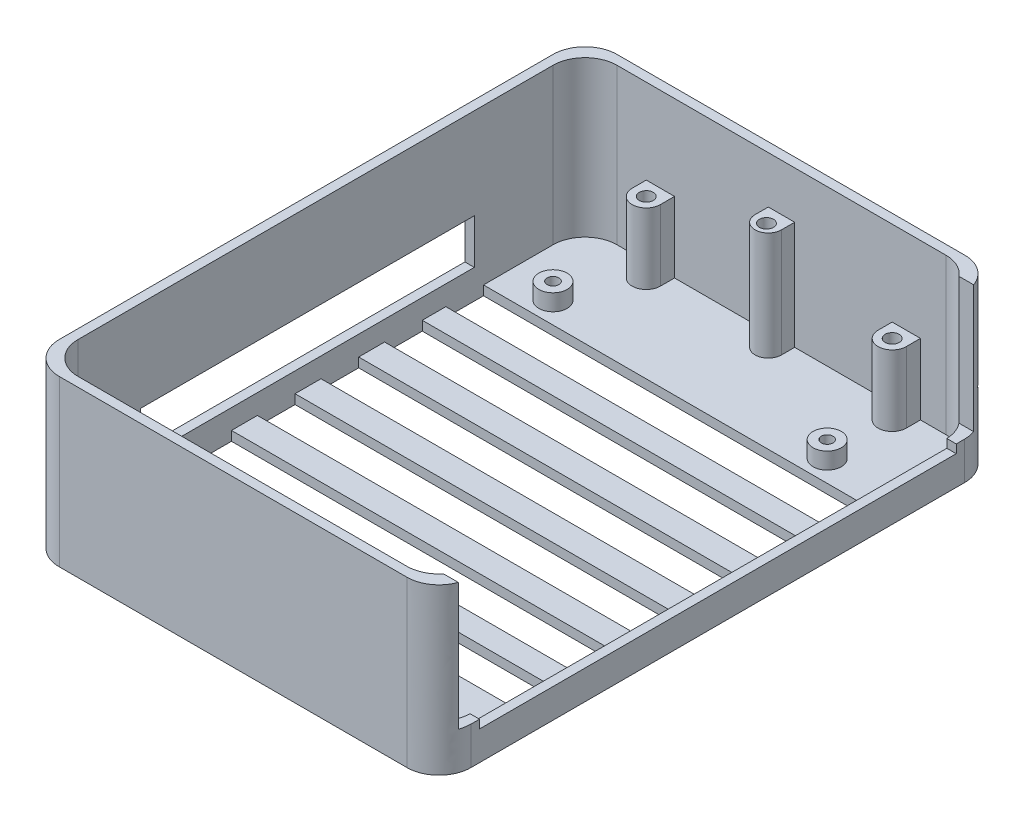
SolidWorks part; units mm, degrees
ref_plane "Front Plane" through (0, 0, 0) normal (0, 0, 1) x (1, 0, 0)
ref_plane "Top Plane" through (0, 0, 0) normal (0, 1, 0) x (1, 0, 0)
ref_plane "Right Plane" through (0, 0, 0) normal (1, 0, 0) x (0, 0, -1)
sketch "Sketch1" plane through (0, 0, 0) normal (0, 1, 0) x (1, 0, 0)
  line L1 (43.7, -59.2) -> (-43.7, -59.2)
  line L2 (43.7, -59.2) -> (43.7, 59.2)
  line L3 (43.7, 59.2) -> (-43.7, 59.2)
  line L4 (-43.7, -59.2) -> (-43.7, 59.2)
  line L5 (43.7, -59.2) -> (-43.7, 59.2) construction
  line L6 (43.7, 59.2) -> (-43.7, -59.2) construction
  point P0 (0, 0)
  dimension "D1" = 118.4
  dimension "D2" = 87.4
extrude "Boss-Extrude1" add sketch "Sketch1" along normal blind 35
sketch "Sketch2" plane through (0, 35, 0) normal (0, 1, 0) x (1, 0, 0)
  line L0 (-43.7, 59.2) -> (-43.7, -59.2) construction
  line L2 (43.7, -59.2) -> (43.7, 59.2) construction
  line L3 (-43.7, -59.2) -> (43.7, -59.2) construction
  line L4 (43.7, 59.2) -> (-43.7, 59.2) construction
  line L5 (-43.7, 59.2) -> (-43.7, -59.2) construction
  line L6 (43.7, -59.2) -> (43.7, 59.2) construction
  line L7 (-43.7, -59.2) -> (43.7, -59.2) construction
  line L8 (43.7, 59.2) -> (-43.7, 59.2) construction
  line L10 (41.7, -57.2) -> (-41.7, -57.2)
  line L11 (41.7, -57.2) -> (41.7, 57.2)
  line L12 (41.7, 57.2) -> (-41.7, 57.2)
  line L13 (-41.7, -57.2) -> (-41.7, 57.2)
  line L14 (41.7, -57.2) -> (-41.7, 57.2) construction
  line L15 (41.7, 57.2) -> (-41.7, -57.2) construction
  point P5 (0, 0)
  dimension "D1" = 2
  dimension "D2" = 2
extrude "Cut-Extrude1" cut sketch "Sketch2" against normal blind 33
sketch "Sketch3" plane through (43.7, 0, 0) normal (1, 0, 0) x (0, 0, -1)
  line L0 (54.7, 35) -> (54.7, 8)
  line L1 (-59.2, 35) -> (59.2, 35) construction
  line L3 (54.7, 8) -> (50.6, 8)
  line L4 (50.6, 8) -> (50.6, 6.2)
  line L5 (50.6, 6.2) -> (-50.6, 6.2)
  line L6 (0, -0.5379) -> (0, 35) construction
  line L7 (-54.7, 35) -> (-54.7, 8)
  line L8 (-54.7, 8) -> (-50.6, 8)
  line L9 (-50.6, 8) -> (-50.6, 6.2)
  line L10 (-59.2, 0) -> (59.2, 0) construction
  point P16 (0, 6.2)
  dimension "D1" = 4.5
  dimension "D2" = 27
  dimension "D3" = 4.1
  dimension "D4" = 1.8
extrude "Cut-Extrude2" cut sketch "Sketch3" against normal blind 33 and the other way through all
fillet "Fillet1" radius 6.8 8 edges at (41.7, 18.5, 57.2) (-41.7, 18.5, -57.2) (-41.7, 18.5, 57.2) (41.7, 18.5, -57.2) (-43.7, 17.5, -59.2) (43.7, 17.5, -59.2) (43.7, 17.5, 59.2) (-43.7, 17.5, 59.2) first distance on face at (0, 18.5, 57.2) first distance on face at (0, 18.5, -57.2) first distance on face at (-41.7, 18.5, 0) first distance on face at (41.7, 15.7, 0) first distance on face at (-43.7, 17.5, 0) first distance on face at (43.7, 15.3667, 0)
sketch "Sketch4" plane through (0, 2, 0) normal (0, 1, 0) x (1, 0, 0)
  line L0 (41.7, 40.2) -> (26.7, 40.2) construction
  line L1 (41.7, 50.4) -> (41.7, -50.4) construction
  line L2 (36.9, 59.2) -> (-36.9, 59.2) construction
  line L3 (26.7, 40.2) -> (-31.5, 40.2) construction
  line L5 (-31.5, 40.2) -> (-31.5, -45.9) construction
  line L6 (26.7, 40.2) -> (26.7, -45.9) construction
  circle A0 centre (-31.5, 40.2) radius 1.25
  circle A1 centre (26.7, 40.2) radius 1.25
  circle A2 centre (-31.5, -45.9) radius 1.25
  circle A3 centre (26.7, -45.9) radius 1.25
  circle A4 centre (-31.5, -45.9) radius 3
  circle A5 centre (26.7, -45.9) radius 3
  circle A6 centre (26.7, 40.2) radius 3
  circle A7 centre (-31.5, 40.2) radius 3
  dimension "D4" = 2.5
  dimension "D5" = 2.5
  dimension "D7" = 2.5
  dimension "D8" = 2.5
  dimension "D9" = 6
  dimension "D10" = 6
  dimension "D11" = 6
  dimension "D12" = 6
  dimension "D1" = 15
  dimension "D2" = 19
  dimension "D3" = 58.2
  dimension "D6" = 86.1
  dimension "D13" = 86.1
extrude "Boss-Extrude2" add sketch "Sketch4" along normal blind 3.5
sketch "Sketch5" plane through (0, 2, 0) normal (0, 1, 0) x (1, 0, 0)
  line L0 (-25.7, -59) -> (-25.7, -54) construction
  line L2 (-25.7, -54) -> (-43.7, -54) construction
  line L3 (-43.7, 52.4) -> (-43.7, -52.4) construction
  line L4 (-25.7, -54) -> (26.3, -54) construction
  line L5 (-25.7, 59.2) -> (-25.7, 54.2) construction
  line L6 (36.9, 59.2) -> (-36.9, 59.2) construction
  line L7 (-25.7, 54.2) -> (26.5, 54.2) construction
  line L9 (-28.7, 54.2) -> (-28.7, 57.2)
  line L10 (-34.9, -57.2) -> (34.9, -57.2) construction
  line L11 (34.9, 57.2) -> (-34.9, 57.2) construction
  line L12 (-22.7, 54.2) -> (-22.7, 57.2)
  line L13 (34.9, 57.2) -> (-34.9, 57.2) construction
  line L14 (23.5, 54.2) -> (23.5, 57.2)
  line L15 (29.5, 54.2) -> (29.5, 57.2)
  line L16 (-28.7, -54) -> (-28.7, -57.2)
  line L17 (-34.9, -57.2) -> (34.9, -57.2) construction
  line L18 (-22.7, -54) -> (-22.7, -57.2)
  line L19 (23.3, -54) -> (23.3, -57.2)
  line L20 (29.3, -54) -> (29.3, -57.2)
  line L21 (-28.7, -57.2) -> (-22.7, -57.2)
  line L22 (23.3, -57.2) -> (29.3, -57.2)
  line L23 (23.5, 57.2) -> (29.5, 57.2)
  line L24 (-28.7, 57.2) -> (-22.7, 57.2)
  circle A0 centre (-25.7, -54) radius 1.5
  circle A1 centre (26.3, -54) radius 1.5
  arc A2 (-22.7, -54) -> (-28.7, -54) centre (-25.7, -54) ccw
  arc A3 (29.3, -54) -> (23.3, -54) centre (26.3, -54) ccw
  circle A5 centre (26.5, 54.2) radius 1.5
  arc A6 (23.5, 54.2) -> (29.5, 54.2) centre (26.5, 54.2) ccw
  circle A7 centre (-25.7, 54.2) radius 1.5
  arc A8 (-28.7, 54.2) -> (-22.7, 54.2) centre (-25.7, 54.2) ccw
  dimension "D4" = 3
  dimension "D5" = 3
  dimension "D6" = 6
  dimension "D7" = 6
  dimension "D9" = 3
  dimension "D10" = 6
  dimension "D11" = 3
  dimension "D12" = 6
  dimension "D1" = 18
  dimension "D2" = 5
  dimension "D3" = 52
  dimension "D8" = 5
extrude "Boss-Extrude4" add sketch "Sketch5" along normal blind 15
sketch "Sketch7" plane through (0, 2, 0) normal (0, 1, 0) x (1, 0, 0)
  circle A0 centre (-25.7, 54.2) radius 1.5 construction
  circle A1 centre (-25.7, 54.2) radius 1.5
  circle A2 centre (26.5, 54.2) radius 1.5 construction
  circle A3 centre (26.5, 54.2) radius 1.5
  circle A4 centre (-25.7, -54) radius 1.5 construction
  circle A5 centre (-25.7, -54) radius 1.5
  circle A6 centre (26.3, -54) radius 1.5 construction
  circle A7 centre (26.3, -54) radius 1.5
extrude "Cut-Extrude3" cut sketch "Sketch7" against normal blind 20
sketch "Sketch9" plane through (0, 2, 0) normal (0, 1, 0) x (1, 0, 0)
  line L0 (0, 57.2) -> (0, -59.2) construction
  line L2 (-36.9, -59.2) -> (36.9, -59.2) construction
  line L3 (0, 57.2) -> (-2.8, 57.2)
  line L5 (34.9, 57.2) -> (-34.9, 57.2) construction
  line L6 (0, 57.2) -> (2.8, 57.2)
  line L7 (-2.8, 57.2) -> (-2.8, 54.4)
  line L8 (2.8, 57.2) -> (2.8, 54.4)
  line L10 (-3, -57.2) -> (-3, -54.4)
  line L12 (2.6, -57.2) -> (2.6, -54.4)
  line L13 (-34.9, -57.2) -> (34.9, -57.2) construction
  line L14 (-3, -57.2) -> (2.6, -57.2)
  line L15 (-2.8, 54.4) -> (2.8, 54.4)
  line L16 (-3, -54.4) -> (2.6, -54.4)
  dimension "D5" = 2.8
  dimension "D1" = 2.8
  dimension "D2" = 2.8
  dimension "D3" = 2.8
  dimension "D4" = 2.8
  dimension "D6" = 5.6
extrude "Boss-Extrude5" add sketch "Sketch9" along normal blind 23
sketch "Sketch10" plane through (0, 2, 0) normal (0, 1, 0) x (1, 0, 0)
  line L3 (2.6, -54.4) -> (-3, -54.4) construction
  line L8 (-3, -54.4) -> (2.6, -54.4)
  line L9 (-2.8, 54.4) -> (2.8, 54.4) construction
  line L12 (-2.8, 54.4) -> (2.8, 54.4)
  arc A3 (2.6, -54.4) -> (-3, -54.4) centre (-0.2, -54.4) ccw
  arc A4 (-2.8, 54.4) -> (2.8, 54.4) centre (0, 54.4) ccw
  dimension "D1" = 5.6
extrude "Boss-Extrude6" add sketch "Sketch10" along normal blind 23
sketch "Sketch11" plane through (0, 25, 0) normal (0, 1, 0) x (1, 0, 0)
  line L0 (0, 57.2) -> (0, 54.0044) construction
  line L1 (2.8, 57.2) -> (-2.8, 57.2) construction
  line L2 (0, -57.2) -> (0, -54.2) construction
  line L3 (-34.9, -57.2) -> (34.9, -57.2) construction
  circle A0 centre (0, 54.0044) radius 1.5
  circle A1 centre (0, -54.2) radius 1.5
  dimension "D1" = 3
  dimension "D3" = 3
  dimension "D2" = 3
extrude "Cut-Extrude4" cut sketch "Sketch11" against normal blind 17
sketch "Sketch12" plane through (0, 2, 0) normal (0, 1, 0) x (1, 0, 0)
  line L0 (-41.7, 50.4) -> (-41.7, -50.4) construction
  line L1 (-41.7, -38.8457) -> (41.7, -38.8457)
  line L2 (-41.7, -38.8457) -> (-41.7, -30.8457)
  line L3 (-41.7, -30.8457) -> (41.7, -30.8457)
  line L4 (41.7, -38.8457) -> (41.7, -30.8457)
  line L5 (41.7, 50.4) -> (41.7, -50.4) construction
  line L6 (41.7, -50.4) -> (41.7, 50.4) construction
  line L7 (-41.7, -25.8457) -> (41.7, -25.8457)
  line L8 (-41.7, -25.8457) -> (-41.7, -17.8457)
  line L9 (-41.7, -17.8457) -> (41.7, -17.8457)
  line L10 (41.7, -25.8457) -> (41.7, -17.8457)
  line L11 (-41.7, -12.3457) -> (41.7, -12.3457)
  line L12 (-41.7, -12.3457) -> (-41.7, -4.3457)
  line L13 (-41.7, -4.3457) -> (41.7, -4.3457)
  line L14 (41.7, -12.3457) -> (41.7, -4.3457)
  line L15 (-41.7, 22.6543) -> (-41.7, 27.6543) construction
  line L16 (-41.7, 1.1543) -> (41.7, 1.1543)
  line L17 (-41.7, 1.1543) -> (-41.7, 9.1543)
  line L18 (-41.7, 9.1543) -> (41.7, 9.1543)
  line L19 (41.7, 1.1543) -> (41.7, 9.1543)
  line L20 (-41.7, 14.6543) -> (41.7, 14.6543)
  line L21 (-41.7, 14.6543) -> (-41.7, 22.6543)
  line L22 (-41.7, 22.6543) -> (41.7, 22.6543)
  line L23 (41.7, 14.6543) -> (41.7, 22.6543)
  line L25 (-41.7, 27.6543) -> (41.7, 27.6543)
  line L26 (-41.7, 27.6543) -> (-41.7, 35.6543)
  line L27 (-41.7, 35.6543) -> (41.7, 35.6543)
  line L28 (41.7, 27.6543) -> (41.7, 35.6543)
  dimension "D1" = 8
  dimension "D2" = 8
  dimension "D3" = 8
  dimension "D4" = 8
  dimension "D5" = 8
  dimension "D6" = 5.5
  dimension "D7" = 5.5
  dimension "D8" = 5
  dimension "D9" = 5.5
  dimension "D10" = 5
  dimension "D11" = 8
extrude "Cut-Extrude5" cut sketch "Sketch12" against normal blind 10
sketch "Sketch15" plane through (0, 5.5, 0) normal (0, 1, 0) x (1, 0, 0)
  circle A0 centre (26.7, -45.9) radius 1.25 construction
  circle A1 centre (-31.5, -45.9) radius 1.25 construction
  circle A2 centre (26.7, 40.2) radius 1.25 construction
  circle A3 centre (-31.5, 40.2) radius 1.25 construction
  circle A4 centre (26.7, -45.9) radius 1.25
  circle A5 centre (-31.5, -45.9) radius 1.25
  circle A6 centre (26.7, 40.2) radius 1.25
  circle A7 centre (-31.5, 40.2) radius 1.25
extrude "Cut-Extrude6" cut sketch "Sketch15" against normal blind 10
sketch "Sketch16" plane through (-43.7, 0, 0) normal (-1, 0, 0) x (0, 0, 1)
  line L0 (0, 0) -> (0, 6.2) construction
  line L1 (-59.2, 0) -> (-33.7, 0) construction
  line L2 (-52.4, 0) -> (52.4, 0) construction
  line L3 (59.2, 0) -> (37.2, 0) construction
  line L4 (-59.2, 6.2) -> (59.2, 6.2) construction
  line L5 (-59.2, 35) -> (-59.2, 0) construction
  line L6 (59.2, 0) -> (59.2, 35) construction
  line L7 (-33.7, 0) -> (-33.7, 35) construction
  line L8 (-52.4, 35) -> (52.4, 35) construction
  line L9 (37.2, 0) -> (37.2, 35) construction
  line L11 (-33.7, 6.2) -> (37.2, 6.2)
  line L12 (-33.7, 6.2) -> (-33.7, 15.7)
  line L13 (-33.7, 15.7) -> (37.2, 15.7)
  line L14 (37.2, 6.2) -> (37.2, 15.7)
  point P17 (-33.7, 6.2)
  dimension "D1" = 6.2
  dimension "D2" = 25.5
  dimension "D3" = 22
  dimension "D4" = 9.5
extrude "Cut-Extrude7" cut sketch "Sketch16" against normal blind 10
